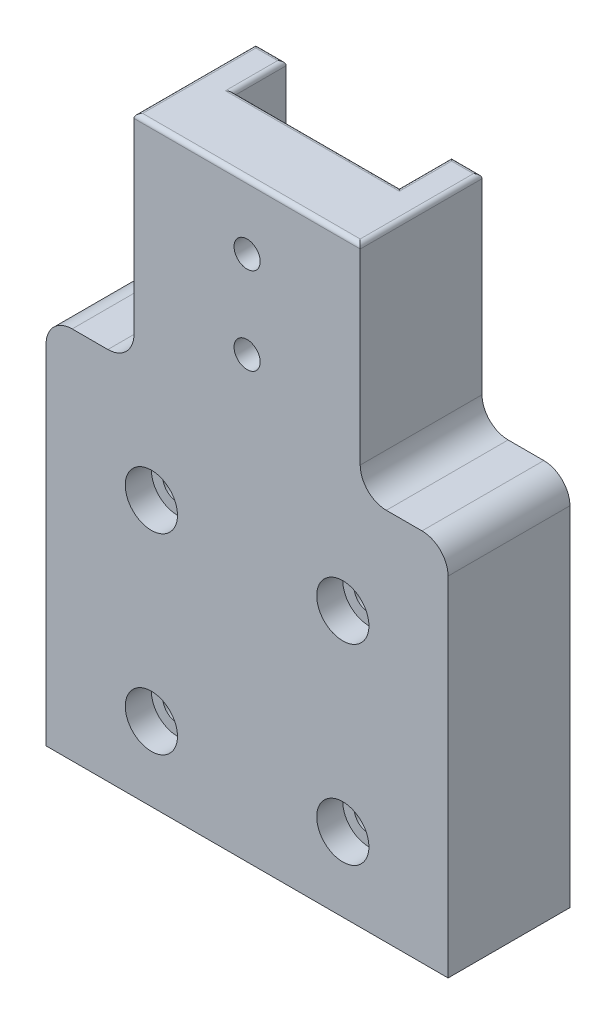
SolidWorks part; units mm, degrees
other "Markup1"
sketch "Sketch9" plane through (-23.1, -13, 8) normal (-0.4776, -0.6311, 0.6112) x (-0.7397, -0.0865, -0.6673)
ref_plane "Front Plane" through (0, 0, 0) normal (0, 0, 1) x (1, 0, 0)
ref_plane "Top Plane" through (0, 0, 0) normal (0, 1, 0) x (1, 0, 0)
ref_plane "Right Plane" through (0, 0, 0) normal (1, 0, 0) x (0, 0, -1)
sketch "Sketch1" plane through (0, 0, 0) normal (0, 1, 0) x (1, 0, 0)
  line L1 (23.1, 7) -> (-23.1, 7)
  line L2 (23.1, 7) -> (23.1, -7)
  line L3 (23.1, -7) -> (-23.1, -7)
  line L4 (-23.1, 7) -> (-23.1, -7)
  line L5 (23.1, 7) -> (-23.1, -7) construction
  line L6 (23.1, -7) -> (-23.1, 7) construction
  point P0 (0, 0)
  dimension "D1" = 14
  dimension "D2" = 46.2
extrude "Boss-Extrude1" add sketch "Sketch1" along normal blind 43
ref_plane "Plane1" through (0, 43, 0) normal (0, 1, 0) x (1, 0, 0)
sketch "Sketch10" plane through (0, 43, 0) normal (0, 1, 0) x (1, 0, 0)
  line L0 (23.1, 7) -> (-23.1, 7) construction
  line L1 (13, -7) -> (-13, -7)
  line L2 (13, -7) -> (13, 7)
  line L3 (13, 7) -> (-13, 7)
  line L4 (-13, -7) -> (-13, 7)
  line L5 (13, -7) -> (-13, 7) construction
  line L6 (13, 7) -> (-13, -7) construction
  point P0 (0, 0)
  dimension "D1" = 26
extrude "Boss-Extrude4" add sketch "Sketch10" along normal blind 25
ref_plane "Plane2" through (0, 68, 0) normal (0, 1, 0) x (1, 0, 0)
sketch "Sketch11" plane through (0, 68, 0) normal (0, 1, 0) x (1, 0, 0)
  line L0 (13, 7) -> (-13, 7) construction
  line L1 (9.5, 1) -> (-9.5, 1)
  line L2 (9.5, 1) -> (9.5, 7)
  line L3 (9.5, 7) -> (-9.5, 7)
  line L4 (-9.5, 1) -> (-9.5, 7)
  line L5 (9.5, 1) -> (-9.5, 7) construction
  line L6 (9.5, 7) -> (-9.5, 1) construction
  line L7 (-13, 7) -> (-13, -7) construction
  point P0 (0, 4)
  point P7 (-9.5, 4)
  dimension "D1" = 19
  dimension "D2" = 6
  dimension "D3" = 13
extrude "Cut-Extrude2" cut sketch "Sketch11" against normal blind 25
fillet "Fillet1" radius 3 4 edges at (-13, 43, 0) (13, 43, 0) (23.1, 43, 0) (-23.1, 43, 0)
fillet "Fillet2" radius 0.5 8 edges at (-13, 68, 0) (-11.25, 68, -7) (-9.5, 68, -4) (0, 68, -1) (9.5, 68, -4) (11.25, 68, -7) (13, 68, 0) (0, 68, 7)
sketch "Sketch12" plane through (0, 0, 0) normal (0, 0, 1) x (1, 0, 0)
  line L0 (-18.4905, 55.5) -> (19.9775, 55.5) construction
  line L1 (-20.1, 43) -> (-16, 43) construction
  line L2 (13, 67.5) -> (13, 46) construction
  circle A0 centre (0, 50.5) radius 1.5
  circle A1 centre (0, 60.5) radius 1.5
  dimension "D1" = 3
  dimension "D2" = 10
  dimension "D3" = 5
  dimension "D4" = 12.5
  dimension "D5" = 13
extrude "Cut-Extrude3" cut sketch "Sketch12" against normal mid plane 20
ref_plane "Plane3" through (0, 0, 0) normal (0, -1, 0) x (-1, 0, 0)
sketch "Sketch13" plane through (0, 0, 0) normal (0, -1, 0) x (-1, 0, 0)
  line L1 (20.3, -2.2) -> (-20.3, -2.2)
  line L2 (20.3, -2.2) -> (20.3, 2.2)
  line L3 (20.3, 2.2) -> (-20.3, 2.2)
  line L4 (-20.3, -2.2) -> (-20.3, 2.2)
  line L5 (20.3, -2.2) -> (-20.3, 2.2) construction
  line L6 (20.3, 2.2) -> (-20.3, -2.2) construction
  point P0 (0, 0)
  dimension "D1" = 4.4
  dimension "D2" = 40.6
extrude "Cut-Extrude4" cut sketch "Sketch13" against normal blind 40
sketch "Sketch14" plane through (0, 0, 0) normal (0, 0, 1) x (1, 0, 0)
  line L0 (-7.7, 0) -> (7.7, 0) construction
  line L1 (20, 0) -> (-20, 0)
  line L2 (20, 0) -> (20, 40)
  line L3 (20, 40) -> (-20, 40)
  line L4 (-20, 0) -> (-20, 40)
  line L5 (20, 0) -> (-20, 40) construction
  line L6 (20, 40) -> (-20, 0) construction
  circle A0 centre (-11, 30.5) radius 1.7
  circle A1 centre (11, 30.5) radius 1.7
  circle A2 centre (11, 8.5) radius 1.7
  circle A3 centre (-11, 8.5) radius 1.7
  point P0 (0, 20)
  point P16 (0, 0)
  point P17 (0, 0)
  point P18 (0, 0)
  point P19 (0, 0)
  dimension "D3" = 3.4
  dimension "D1" = 40
  dimension "D2" = 40
  dimension "D4" = 9.5
  dimension "D5" = 9
  dimension "D6" = 8.5
  dimension "D7" = 9
extrude "Cut-Extrude6" cut sketch "Sketch14" against normal mid plane 40 contours A0 | A1 | A2 | A3
ref_plane "Plane4" through (0, 0, -7) normal (0, 0, -1) x (-1, 0, 0)
sketch "Sketch15" plane through (0, 0, -7) normal (0, 0, -1) x (-1, 0, 0)
  line L0 (-11, 33.6754) -> (-11, 30.5) construction
  line L1 (-11, 33.6754) -> (-13.75, 32.0877)
  line L2 (-13.75, 32.0877) -> (-13.75, 28.9123)
  line L3 (-13.75, 28.9123) -> (-11, 27.3246)
  line L4 (-11, 27.3246) -> (-8.25, 28.9123)
  line L5 (-8.25, 28.9123) -> (-8.25, 32.0877)
  line L6 (-8.25, 32.0877) -> (-11, 33.6754)
  line L7 (11, 33.6754) -> (8.25, 32.0877)
  line L8 (8.25, 32.0877) -> (8.25, 28.9123)
  line L9 (8.25, 28.9123) -> (11, 27.3246)
  line L10 (11, 27.3246) -> (13.75, 28.9123)
  line L11 (13.75, 28.9123) -> (13.75, 32.0877)
  line L12 (13.75, 32.0877) -> (11, 33.6754)
  line L13 (11, 11.6754) -> (8.25, 10.0877)
  line L14 (8.25, 10.0877) -> (8.25, 6.9123)
  line L15 (8.25, 6.9123) -> (11, 5.3246)
  line L16 (11, 5.3246) -> (13.75, 6.9123)
  line L17 (13.75, 6.9123) -> (13.75, 10.0877)
  line L18 (13.75, 10.0877) -> (11, 11.6754)
  line L19 (-11, 11.6754) -> (-13.75, 10.0877)
  line L20 (-13.75, 10.0877) -> (-13.75, 6.9123)
  line L21 (-13.75, 6.9123) -> (-11, 5.3246)
  line L22 (-11, 5.3246) -> (-8.25, 6.9123)
  line L23 (-8.25, 6.9123) -> (-8.25, 10.0877)
  line L24 (-8.25, 10.0877) -> (-11, 11.6754)
  line L25 (11, 33.6754) -> (11, 30.5) construction
  line L26 (11, 8.5) -> (11, 11.6754) construction
  line L27 (-11, 8.5) -> (-11, 11.6754) construction
  circle A0 centre (-11, 30.5) radius 2.75 construction
  circle A1 centre (11, 30.5) radius 2.75 construction
  circle A2 centre (11, 8.5) radius 2.75 construction
  circle A3 centre (-11, 8.5) radius 2.75 construction
  dimension "D1" = 5.5
  dimension "D2" = 5.5
  dimension "D3" = 5.5
  dimension "D4" = 5.5
extrude "Cut-Extrude7" cut sketch "Sketch15" against normal blind 4
ref_plane "Plane5" through (0, 0, 7) normal (0, 0, 1) x (1, 0, 0)
sketch "Sketch16" plane through (0, 0, 7) normal (0, 0, 1) x (1, 0, 0)
  circle A0 centre (-11, 30.5) radius 3
  circle A1 centre (11, 30.5) radius 3
  circle A2 centre (11, 8.5) radius 3
  circle A3 centre (-11, 8.5) radius 3
  dimension "D1" = 6
extrude "Cut-Extrude8" cut sketch "Sketch16" against normal blind 3
